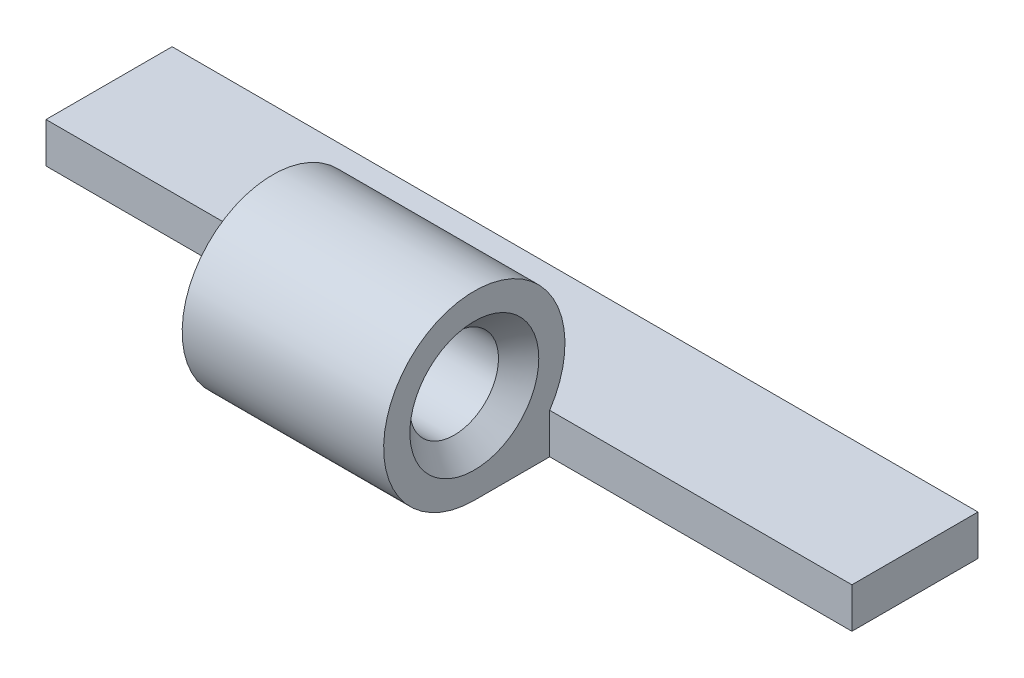
SolidWorks part; units mm, degrees
ref_plane "Ebene vorne" through (0, 0, 0) normal (0, 0, 1) x (1, 0, 0)
ref_plane "Ebene oben" through (0, 0, 0) normal (0, 1, 0) x (1, 0, 0)
ref_plane "Ebene rechts" through (0, 0, 0) normal (1, 0, 0) x (0, 0, -1)
sketch "Skizze2" plane through (0, 0, 0) normal (0, 1, 0) x (1, 0, 0)
  line L1 (-7.5, 2.5) -> (7.5, 2.5)
  line L2 (-7.5, 2.5) -> (-7.5, -2.5)
  line L3 (-7.5, -2.5) -> (7.5, -2.5)
  line L4 (7.5, 2.5) -> (7.5, -2.5)
  line L5 (-7.5, 2.5) -> (7.5, -2.5) construction
  line L6 (-7.5, -2.5) -> (7.5, 2.5) construction
  point P0 (0, 0)
  dimension "D1" = 15
  dimension "D2" = 5
extrude "Aufsatz-Linear austragen1" add sketch "Skizze2" along normal blind 1
sketch "Skizze3" plane through (7.5, 0, 0) normal (1, 0, 0) x (0, 0, -1)
  circle A0 centre (-2.5, 2.25) radius 2.25
  circle A1 centre (-2.5, 2.25) radius 1.1
  dimension "D1" = 2.2
  dimension "D2" = 4.5
extrude "Aufsatz-Linear austragen2" add sketch "Skizze3" against normal up to surface (15 mm away) up to face at (-7.5, 0.5, 0)
ref_plane "Tangential Ebene" through (0, 0, 0.25) normal (0, 0, -1) x (-1, 0, 0)
sketch "Skizze5" plane through (7.5, 0, 0) normal (1, 0, 0) x (0, 0, -1)
  line L0 (-0.6292, 1) -> (-0.6292, 0)
  line L1 (-0.6292, 0) -> (-2.5, 0)
  line L3 (2.5, 1) -> (-0.6292, 1)
  line L4 (-2.5, 0) -> (2.5, 0)
  line L5 (2.5, 0) -> (2.5, 1)
  line L6 (2.5, 1) -> (-0.6292, 1) construction
  line L7 (-2.5, 0) -> (2.5, 0) construction
  line L8 (2.5, 0) -> (2.5, 1) construction
  arc A1 (-0.6292, 1) -> (-2.5, 0) centre (-2.5, 2.25) ccw
  arc A2 (-0.6292, 1) -> (-2.5, 0) centre (-2.5, 2.25) ccw
  dimension "D1" = 0
extrude "Schnitt-Linear austragen1" cut sketch "Skizze5" against normal blind 5
pattern_linear "Lineares Muster1" count 2 spacing 10 along (-1, 0, 0) of "Schnitt-Linear austragen1"
ref_plane "Spiegelebene" through (0, 0, 0) normal (1, 0, 0) x (0, 0, -1)
sketch "Skizze7" plane through (7.5, 0, 0) normal (1, 0, 0) x (0, 0, -1)
  line L1 (2.5, 1) -> (-0.6292, 1)
  line L2 (2.5, 1) -> (2.5, 0)
  line L3 (2.5, 0) -> (-0.6292, 0)
  line L4 (-0.6292, 1) -> (-0.6292, 0)
extrude "Verbreiterung" add sketch "Skizze7" along normal blind 2.5
mirror "Spiegeln1" about plane through (0, 0, 0) normal (1, 0, 0) of "Verbreiterung"
ref_axis "Achse1" through (-2.5, 2.25, 2.5) along (1, 0, 0)
chamfer "Fase1" distance 0.5 angle 45 2 edges at (-2.5, 2.25, 1.4) (2.5, 2.25, 1.4)
